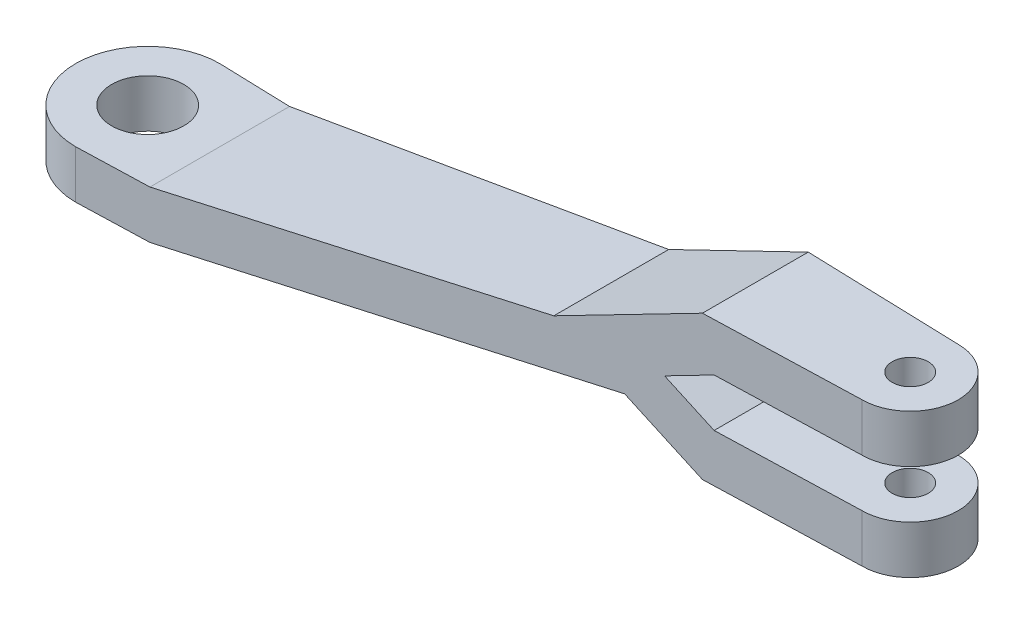
SolidWorks part; units mm, degrees
ref_plane "Спереди" through (0, 0, 0) normal (0, 0, 1) x (1, 0, 0)
ref_plane "Сверху" through (0, 0, 0) normal (0, 1, 0) x (1, 0, 0)
ref_plane "Справа" through (0, 0, 0) normal (1, 0, 0) x (0, 0, -1)
sketch "Эскиз1" plane through (0, 0, 0) normal (0, 1, 0) x (1, 0, 0)
  line L0 (0, 0) -> (-31.75, 0) construction
  line L1 (-31.75, 3) -> (0, 2)
  line L2 (-31.75, -3) -> (0, -2)
  circle A0 centre (0, 0) radius 0.75
  circle A1 centre (-31.75, 0) radius 1.5
  circle A2 centre (-31.75, 0) radius 3
  circle A3 centre (0, 0) radius 2
extrude "Бобышка-Вытянуть1" add sketch "Эскиз1" along normal blind 6 and the other way blind 6 contours L0 A3 L1 A2 | A3 L0 A2 L2 | L2 A2 A1 L1 | A0 A3 region at (-16.2798, 0, -1.285) region at (-29.6248, 0, 1.9954) region at (-16.2798, 0, 1.285) region at (-1.3742, 0, -1.3742)
sketch "Эскиз2" plane through (0, 0, 0) normal (0, 0, 1) x (1, 0, 0)
  line L0 (-34.75, -0.25) -> (-34.75, -2)
  line L1 (-34.75, 6) -> (-34.75, -6) construction
  line L2 (-7.976, 3) -> (-8.8704, 4.7889)
  line L3 (2, 6) -> (-6.4481, 6)
  line L4 (-34.75, -0.25) -> (-34.75, -2.25) construction
  line L5 (-6.4481, 6) -> (-12.4481, 3)
  line L6 (2, 6) -> (-6.4481, 6)
  line L7 (-34.75, -2.25) -> (-28.75, -2.25)
  line L8 (2, 2) -> (2, 0)
  line L9 (2, -6) -> (2, 6) construction
  line L10 (2, 4) -> (-5.976, 4)
  line L11 (-5.976, 4) -> (-7.976, 3)
  line L12 (-5.976, 2) -> (-7.976, 3)
  line L13 (2, 2) -> (-5.976, 2)
  line L14 (-12.4481, 3) -> (-28.75, -0.25)
  line L16 (-6.4481, 0) -> (-9.5884, 1.5701)
  line L17 (-5, 6) -> (-34.75, 6)
  line L18 (-47.0537, 20.7159) -> (15.8126, 20.7159)
  line L19 (-34.75, -6) -> (-5, -6)
  line L20 (-28.75, -2.25) -> (-9.5884, 1.5701)
  line L21 (-34.75, -2.25) -> (-34.75, -0.25)
  line L22 (-34.75, -0.25) -> (-28.75, -0.25)
  line L23 (-28.75, -0.25) -> (-12.4481, 3)
  line L24 (-47.0537, 20.7159) -> (-47.0537, -16.9614)
  line L25 (-47.0537, -16.9614) -> (15.8126, -16.9614)
  line L26 (15.8126, 20.7159) -> (15.8126, -16.9614)
  line L27 (-28.75, -2.25) -> (-9.5884, 1.5701)
  line L28 (-6.4481, 0) -> (2, 0)
  line L29 (2, 2) -> (-5.976, 2)
  line L30 (-7.976, 3) -> (-5.976, 4)
  line L31 (2, 4) -> (2, 6)
  point P20 (2, 3)
  point P24 (-34.75, 0)
  dimension "D1" = 2
  dimension "D3" = 8.25
  dimension "D4" = 2
  dimension "D5" = 1
extrude "Вырез-Вытянуть1" cut sketch "Эскиз2" against normal through all and the other way through all contours L19 | L11 L10 | L12 L13 region at (-15.6205, 19.983, 0)
